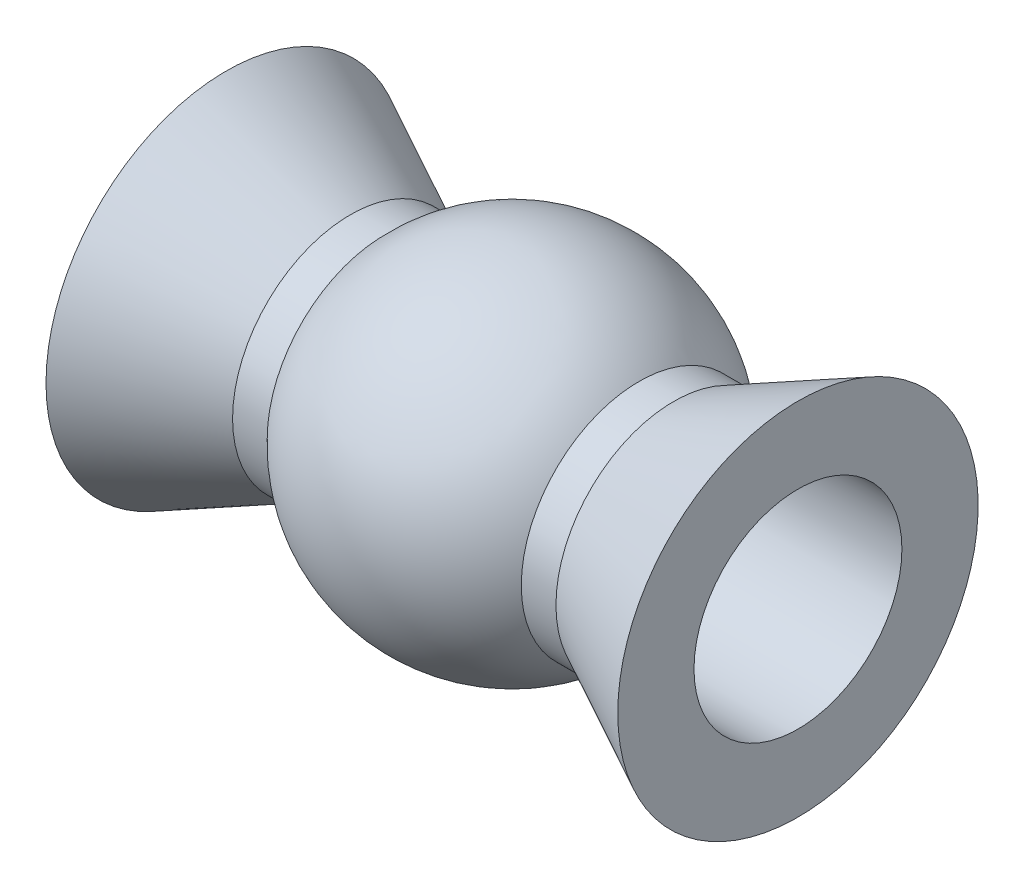
SolidWorks part; units mm, degrees
ref_plane "Front Plane" through (0, 0, 0) normal (0, 0, 1) x (1, 0, 0)
ref_plane "Top Plane" through (0, 0, 0) normal (0, 1, 0) x (1, 0, 0)
ref_plane "Right Plane" through (0, 0, 0) normal (1, 0, 0) x (0, 0, -1)
ref_axis "Axis1" through (4.5375, 0, 0) along (-1, 0, 0)
sketch "Sketch1" plane through (0, 0, 0) normal (0, 1, 0) x (1, 0, 0)
  line L0 (-4.125, 0) -> (4.125, 0)
  line L1 (-4.125, 0) -> (-4.125, 2.6)
  line L2 (-1.833, 1.7) -> (-2.333, 1.7)
  line L3 (-2.333, 1.7) -> (-4.125, 2.6)
  line L4 (0, 2.5) -> (0, 0) construction
  line L5 (4.125, 0) -> (4.125, 2.6)
  line L6 (2.333, 1.7) -> (4.125, 2.6)
  line L7 (1.833, 1.7) -> (2.333, 1.7)
  arc A0 (-1.833, 1.7) -> (1.833, 1.7) centre (0, 0) cw
  dimension "D1" = 2.6
  dimension "D2" = 2.5
  dimension "D3" = 4.125
  dimension "D4" = 0.5
  dimension "D5" = 1.7
revolve "Revolve1" add sketch "Sketch1" angle 360 about L0
sketch "Sketch2" plane through (4.125, 0, 0) normal (1, 0, 0) x (0, 0, -1)
  circle A0 centre (0, 0) radius 1.5
  dimension "D1" = 3
extrude "Cut-Extrude1" cut sketch "Sketch2" against normal through all contours A0
